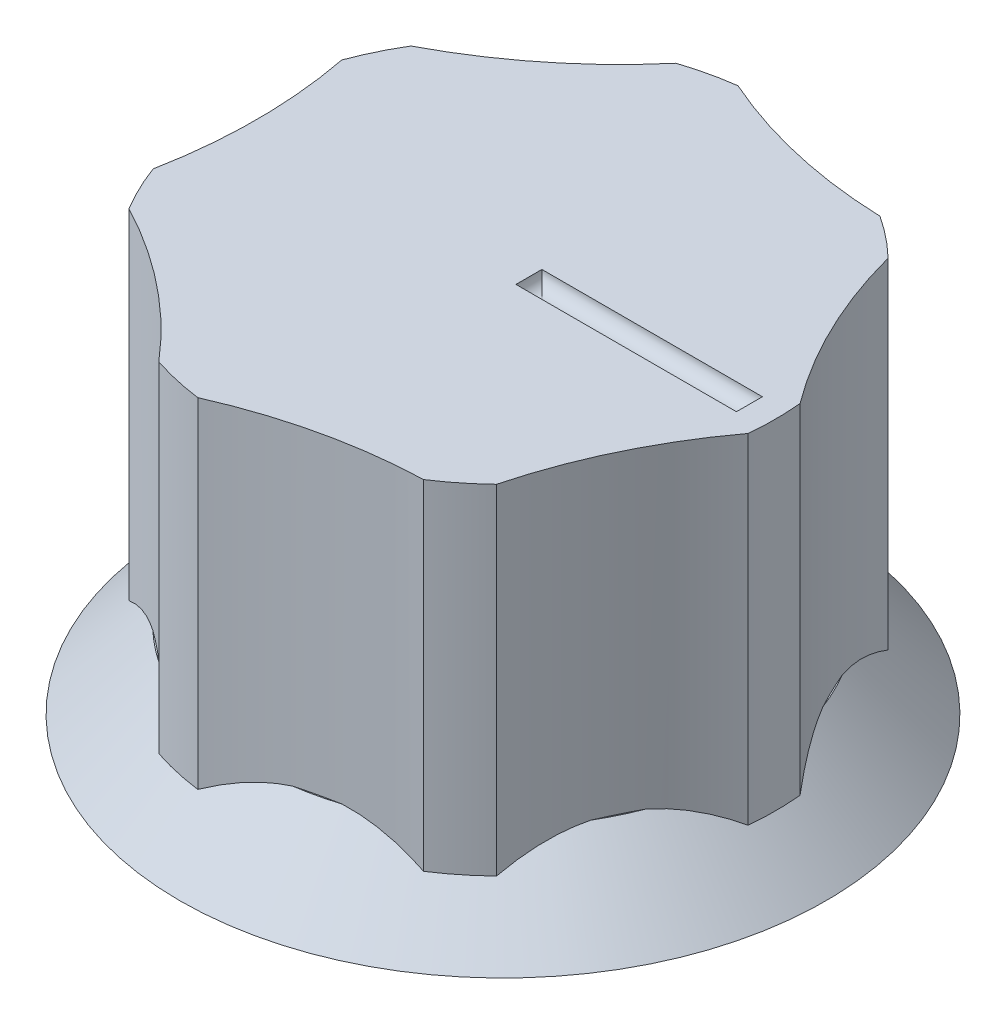
SolidWorks part; units mm, degrees
ref_plane "Front Plane" through (0, 0, 0) normal (0, 0, 1) x (1, 0, 0)
ref_plane "Top Plane" through (0, 0, 0) normal (0, 1, 0) x (1, 0, 0)
ref_plane "Right Plane" through (0, 0, 0) normal (1, 0, 0) x (0, 0, -1)
sketch "Sketch1" plane through (0, 0, 0) normal (0, 1, 0) x (1, 0, 0)
  circle A0 centre (0, 0) radius 12.65
extrude "Boss-Extrude1" add sketch "Sketch1" along normal blind 3
sketch "Sketch2" plane through (0, 3, 0) normal (0, 1, 0) x (1, 0, 0)
  line L0 (0, 0) -> (9.4602, 4.5558) construction
  line L1 (0, 0) -> (10.4524, 0.9985) construction
  line L2 (0, 0) -> (7.2976, 7.5495) construction
  circle A0 centre (0, 0) radius 10.5
  circle A1 centre (0, 0) radius 9.5 construction
  arc A2 (10.4524, 0.9985) -> (7.2976, 7.5495) centre (25.703, 12.3779) cw
  arc A3 (7.2976, -7.5495) -> (10.4524, -0.9985) centre (25.703, -12.3779) cw
  arc A4 (-1.3524, -10.4125) -> (5.7363, -8.7946) centre (6.3481, -27.8129) cw
  arc A5 (-8.9841, -5.4347) -> (-3.2993, -9.9682) centre (-17.787, -22.3042) cw
  arc A6 (-9.8505, 3.6355) -> (-9.8505, -3.6355) centre (-28.5282, 0) cw
  arc A7 (-3.2993, 9.9682) -> (-8.9841, 5.4347) centre (-17.787, 22.3042) cw
  arc A8 (5.7363, 8.7946) -> (-1.3524, 10.4125) centre (6.3481, 27.8129) cw
  point P30 (0, 0)
  dimension "D1" = 1
  dimension "D2" = 7
extrude "Boss-Extrude3" add sketch "Sketch2" along normal blind 12.1 contours A0 A8 A7 A6 A5 A4 A3 A2 region at (0, 3, 0)
chamfer "Chamfer2" distance 3.2 distance2 3.1 1 edges at (0, 3, 12.65) first distance on face at (0, 3, 12.65)
sketch "Sketch4" plane through (0, 15.1, 0) normal (0, 1, 0) x (1, 0, 0)
  line L0 (0, 0) -> (10.5, 0) construction
  line L2 (1, -0.5) -> (9.5, -0.5)
  line L3 (1, -0.5) -> (1, 0.5)
  line L4 (1, 0.5) -> (9.5, 0.5)
  line L5 (9.5, -0.5) -> (9.5, 0.5)
  line L6 (1, -0.5) -> (9.5, 0.5) construction
  line L7 (1, 0.5) -> (9.5, -0.5) construction
  arc A0 (10.4524, -0.9985) -> (10.4524, 0.9985) centre (0, 0) ccw construction
  point P6 (5.25, 0)
  point P8 (5.25, 0)
  dimension "D1" = 1
  dimension "D2" = 8.5
extrude "Cut-Extrude2" cut sketch "Sketch4" against normal blind 0.5
fillet "Fillet1" radius 0.5 4 edges at (9.5, 14.6, 0) (5.25, 14.6, -0.5) (5.25, 14.6, 0.5) (1, 14.6, 0)
sketch "Sketch7" plane through (0, 0, 0) normal (0, -1, 0) x (1, 0, 0)
  circle A0 centre (0, 0) radius 8
extrude "Cut-Extrude3" cut sketch "Sketch7" against normal blind 2
sketch "Sketch8" plane through (0, 2, 0) normal (0, -1, 0) x (-1, 0, 0)
  circle A0 centre (0, 0) radius 3
extrude "Cut-Extrude4" cut sketch "Sketch8" against normal blind 8
